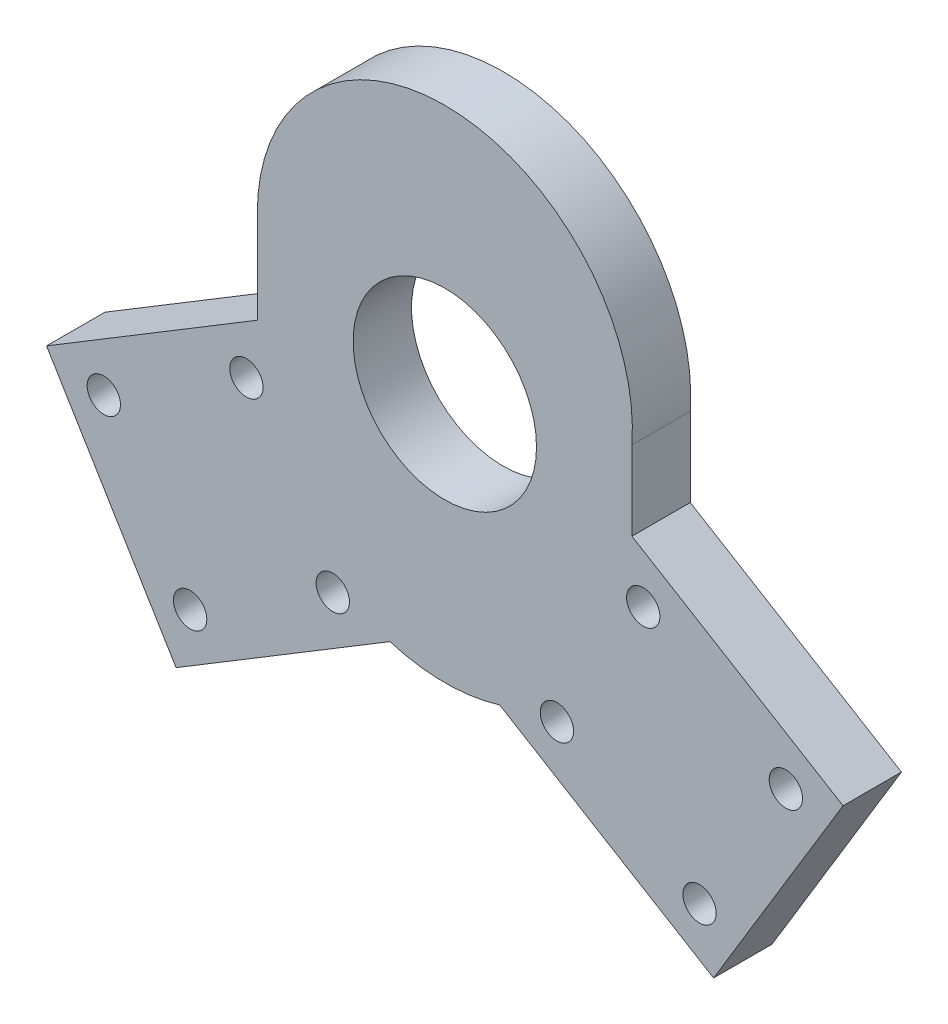
SolidWorks part; units mm, degrees
ref_plane "Front Plane" through (0, 0, 0) normal (0, 0, 1) x (1, 0, 0)
ref_plane "Top Plane" through (0, 0, 0) normal (0, 1, 0) x (1, 0, 0)
ref_plane "Right Plane" through (0, 0, 0) normal (1, 0, 0) x (0, 0, -1)
sketch "Sketch2" plane through (0, 0, 0) normal (0, 0, 1) x (1, 0, 0)
  line L8 (0, 0) -> (0, -22.5) construction
  line L9 (0, 0) -> (6.5784, -21.5169)
  line L10 (0, 0) -> (-6.5784, -21.5169)
  line L11 (6.5784, -21.5169) -> (22.1146, 4.1469)
  line L12 (6.5784, -21.5169) -> (32.2421, -37.053)
  line L13 (22.1146, 4.1469) -> (47.7783, -11.3893)
  line L14 (32.2421, -37.053) -> (47.7783, -11.3893)
  line L15 (-6.5784, -21.5169) -> (-22.1146, 4.1469)
  line L16 (-6.5784, -21.5169) -> (-32.2421, -37.053)
  line L17 (-22.1146, 4.1469) -> (-47.7783, -11.3893)
  line L18 (-32.2421, -37.053) -> (-47.7783, -11.3893)
  line L24 (22.1146, 17.2594) -> (22.1146, 4.1469)
  line L30 (0, 0) -> (0, 15)
  line L31 (-22.5, 15) -> (-22.5, 0)
  line L32 (-22.5, 15) -> (22.4447, 15)
  line L33 (-22.5, 0) -> (22.4447, 0)
  line L34 (22.4447, 15) -> (22.4447, 0)
  circle A0 centre (0, 0) radius 22.5
  circle A2 centre (0, 15) radius 22.5
  dimension "D5" = 45
  dimension "D8" = 15
  dimension "D9" = 45
  dimension "D1" = 17
  dimension "D2" = 17
  dimension "D3" = 30
  dimension "D4" = 30
  dimension "D6" = 30
  dimension "D7" = 30
extrude "Boss-Extrude1" add sketch "Sketch2" along normal blind 7 contours A0 | L15 L16 L18 L17 | L11 L12 L14 L13 | A2 | L31 L32 L34 L33
sketch "Sketch4" plane through (0, 0, 7) normal (0, 0, 1) x (1, 0, 0)
  line L0 (-22.1146, 4.1469) -> (-6.5784, -21.5169)
  line L1 (-22.5, 3.9135) -> (-47.7783, -11.3893) construction
  line L2 (-6.5784, -21.5169) -> (-32.2421, -37.053) construction
  line L3 (-32.2421, -37.053) -> (-47.7783, -11.3893) construction
  line L4 (6.5784, -21.5169) -> (22.1146, 4.1469)
  line L7 (6.5784, -21.5169) -> (32.2421, -37.053) construction
  line L8 (22.4447, 3.947) -> (47.7783, -11.3893) construction
  line L9 (32.2421, -37.053) -> (47.7783, -11.3893) construction
  circle A0 centre (-40.9116, -13.0772) radius 2
  circle A1 centre (-23.8025, -2.7198) radius 2
  circle A2 centre (-13.445, -19.8289) radius 2
  circle A3 centre (-30.5542, -30.1864) radius 2
  circle A4 centre (23.8025, -2.7198) radius 2
  circle A6 centre (13.445, -19.8289) radius 2
  circle A7 centre (40.9116, -13.0772) radius 2
  circle A8 centre (30.5542, -30.1864) radius 2
  dimension "D10" = 4
  dimension "D11" = 4
  dimension "D12" = 4
  dimension "D13" = 4
  dimension "D19" = 4
  dimension "D20" = 4
  dimension "D25" = 4
  dimension "D26" = 4
  dimension "D1" = 30
  dimension "D2" = 5
  dimension "D3" = 5
  dimension "D4" = 5
  dimension "D5" = 5
  dimension "D6" = 5
  dimension "D7" = 5
  dimension "D8" = 5
  dimension "D9" = 5
  dimension "D14" = 30
  dimension "D15" = 5
  dimension "D16" = 5
  dimension "D17" = 5
  dimension "D18" = 5
  dimension "D21" = 5
  dimension "D22" = 5
  dimension "D23" = 5
  dimension "D24" = 5
extrude "Cut-Extrude1" cut sketch "Sketch4" against normal blind 10 contours A0 | A1 | A2 | A3 | A6 | A4 | A7 | A8
sketch "Sketch5" plane through (0, 0, 7) normal (0, 0, 1) x (1, 0, 0)
  line L0 (0, 22.5) -> (0, -22.5)
  arc A0 (-6.5784, -21.5169) -> (6.5784, -21.5169) centre (0, 0) ccw construction
  arc A1 (-6.5784, -21.5169) -> (6.5784, -21.5169) centre (0, 0) ccw construction
  circle A2 centre (0, 7.5) radius 11
  dimension "D2" = 22
  dimension "D1" = 30
extrude "Cut-Extrude2" cut sketch "Sketch5" against normal blind 10 contours A2
